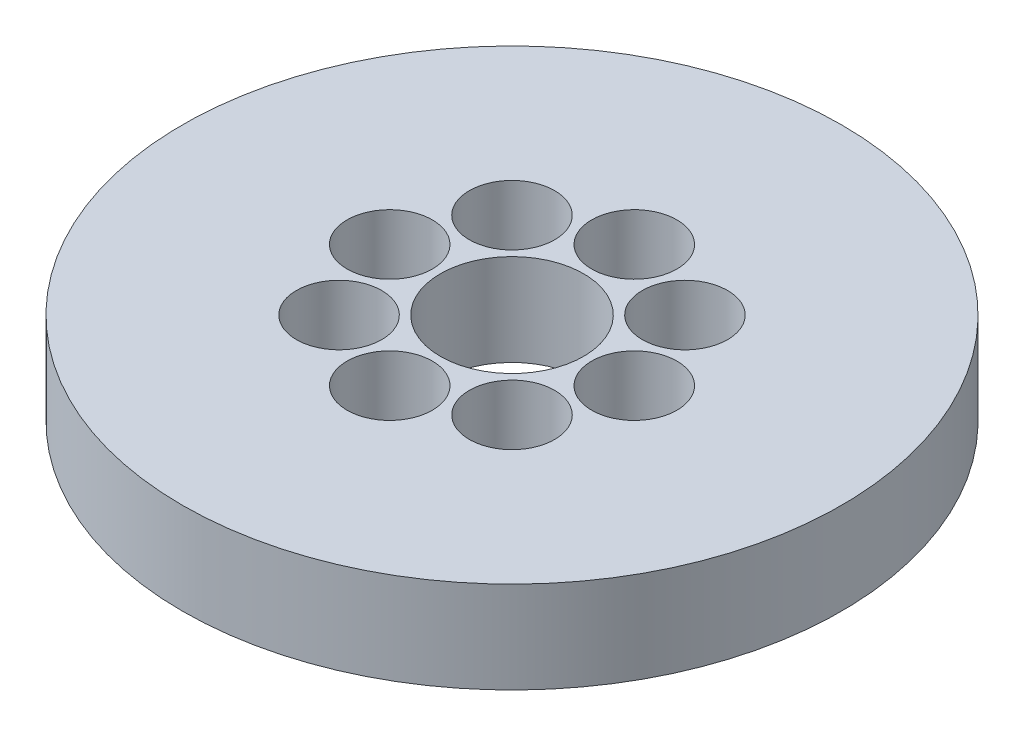
SolidWorks part; units mm, degrees
ref_plane "Front Plane" through (0, 0, 0) normal (0, 0, 1) x (1, 0, 0)
ref_plane "Top Plane" through (0, 0, 0) normal (0, 1, 0) x (1, 0, 0)
ref_plane "Right Plane" through (0, 0, 0) normal (1, 0, 0) x (0, 0, -1)
sketch "Sketch1" plane through (0, 0, 0) normal (0, 1, 0) x (1, 0, 0)
  circle A0 centre (0, 0) radius 57.5
  dimension "FLANGE_OD" = 115
extrude "Boss-Extrude1" add sketch "Sketch1" along normal blind 16
sketch "Sketch2" plane through (0, 0, 0) normal (0, 1, 0) x (1, 0, 0)
  circle A0 centre (0, 0) radius 12.5
  dimension "BORE_D" = 25
extrude "Cut-Extrude1" cut sketch "Sketch2" along normal through all
sketch "Sketch3" plane through (0, 16, 0) normal (0, 1, 0) x (1, 0, 0)
  circle A0 centre (0, 0) radius 21.3365 construction
  circle A1 centre (-21.3365, 0) radius 7.4393
  dimension "BOLT_D" = 14.8786
  dimension "BOLT_PCD" = 42.6731
extrude "Cut-Extrude2" cut sketch "Sketch3" against normal blind 12.433
pattern_circular "CirPattern1" count 8 over 360 about axis through (0, 0, 0) along (0, 1, 0) of "Cut-Extrude2"
